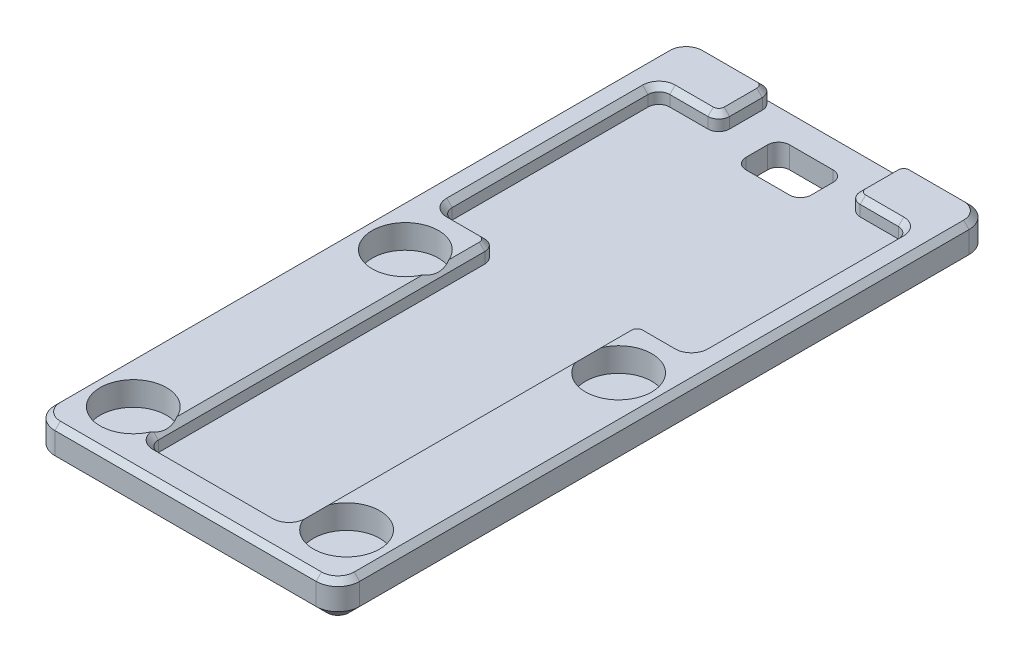
SolidWorks part; units mm, degrees
ref_plane "Front Plane" through (0, 0, 0) normal (0, 0, 1) x (1, 0, 0)
ref_plane "Top Plane" through (0, 0, 0) normal (0, 1, 0) x (1, 0, 0)
ref_plane "Right Plane" through (0, 0, 0) normal (1, 0, 0) x (0, 0, -1)
sketch "Sketch1" plane through (0, 0, 0) normal (0, 1, 0) x (1, 0, 0)
  line L1 (0, 0) -> (28, 0)
  line L2 (0, 0) -> (0, -60)
  line L3 (0, -60) -> (28, -60)
  line L4 (28, 0) -> (28, -60)
  line L5 (8, 0) -> (20, 0)
  line L6 (8, 0) -> (8, -5)
  line L7 (8, -5) -> (20, -5)
  line L8 (20, 0) -> (20, -5)
  line L9 (2.5, -5) -> (25.5, -5)
  line L10 (2.5, -5) -> (2.5, -25)
  line L11 (2.5, -25) -> (25.5, -25)
  line L12 (25.5, -5) -> (25.5, -25)
  line L13 (7.5, -25) -> (20.5, -25)
  line L14 (7.5, -25) -> (7.5, -57)
  line L15 (7.5, -57) -> (20.5, -57)
  line L16 (20.5, -25) -> (20.5, -57)
  circle A0 centre (23.8, -55) radius 3.05
  circle A1 centre (4.2, -30) radius 3.05
  circle A2 centre (23.8, -30) radius 3.05
  circle A3 centre (4.2, -55) radius 3.05
  point P13 (14, -5)
  point P14 (14, 0)
  point P19 (14, -25)
  point P20 (14, -25)
  dimension "D14" = 4.2
  dimension "D1" = 28
  dimension "D2" = 60
  dimension "D3" = 12
  dimension "D4" = 8
  dimension "D5" = 5
  dimension "D6" = 23
  dimension "D7" = 20
  dimension "D8" = 0
  dimension "D9" = 0
  dimension "D10" = 32
  dimension "D11" = 0
  dimension "D12" = 0
  dimension "D13" = 13
  dimension "D15" = 4.2
  dimension "D16" = 4.2
  dimension "D17" = 4.2
  dimension "D18" = 5
  dimension "D19" = 5
  dimension "D20" = 5
  dimension "D21" = 5
extrude "Boss-Extrude1" add sketch "Sketch1" along normal blind 3.5 contours L11 L16 L15 L14 L10 L9 L6 L1 L2 L3 L4 L8 L12 A3 A2 A1 A0 region at (4, 0, 0.6621)
extrude "Boss-Extrude2" add sketch "Sketch1<3>" along normal blind 2 contours L16 L11 L14 L15 | L12 L9 L7 L10 L11 | L8 L1 L6 L7 region at (14, 0, 2.5) region at (14, 0, 15) region at (14, 0, 41)
sketch "Sketch1<3>" plane through (0, 0, 0) normal (0, 1, 0) x (1, 0, 0) same geometry as "Sketch1"
extrude "Boss-Extrude3" add sketch "Sketch1<4>" along normal blind 1.3 contours A1 | A2 | A3 | A0 region at (23.8, 0, 55) region at (4.2, 0, 30) region at (23.8, 0, 30) region at (4.2, 0, 55)
sketch "Sketch1<4>" plane through (0, 0, 0) normal (0, 1, 0) x (1, 0, 0) same geometry as "Sketch1"
sketch "Sketch2" plane through (0, 2, 0) normal (0, 1, 0) x (1, 0, 0)
  line L0 (8, 0) -> (20, 0) construction
  line L1 (11, -2.5) -> (17, -2.5)
  line L2 (11, -2.5) -> (11, -6.5)
  line L3 (11, -6.5) -> (17, -6.5)
  line L4 (17, -2.5) -> (17, -6.5)
  point P6 (14, -6.5)
  point P7 (14, 0)
  dimension "D1" = 2.5
  dimension "D2" = 6
  dimension "D3" = 0
  dimension "D4" = 4
extrude "Cut-Extrude1" cut sketch "Sketch2" against normal blind 4
fillet "Fillet1" radius 1 4 edges at (11, 1, 6.5) (17, 1, 6.5) (17, 1, 2.5) (11, 1, 2.5)
fillet "Fillet2" radius 1 10 edges at (20.5, 2.75, 57) (7.5, 2.75, 57) (2.5, 2.75, 25) (7.5, 2.75, 25) (20.5, 2.75, 25) (25.5, 2.75, 25) (25.5, 2.75, 5) (20, 2.75, 5) (2.5, 2.75, 5) (8, 2.75, 5)
fillet "Fillet3" radius 1 2 edges at (20, 2.75, 0) (8, 2.75, 0)
fillet "Fillet4" radius 2 4 edges at (28, 1.75, 60) (0, 1.75, 60) (28, 1.75, 0) (0, 1.75, 0)
chamfer "Chamfer1" distance 1 angle 45 8 edges at (0, 0, 30) (0.5858, 0, 0.5858) (0.5858, 0, 59.4142) (14, 0, 0) (14, 0, 60) (27.4142, 0, 0.5858) (27.4142, 0, 59.4142) (28, 0, 30)
chamfer "Chamfer2" distance 0.5 angle 45 32 edges at (7.7929, 3.5, 56.7071) (7.5, 3.5, 41) (14, 3.5, 57) (7.2071, 3.5, 25.2929) (20.2071, 3.5, 56.7071) (5, 3.5, 25) (20.5, 3.5, 41) (2.7929, 3.5, 24.7071) (20.7929, 3.5, 25.2929) (2.5, 3.5, 15) (23, 3.5, 25) (2.7929, 3.5, 5.2929) (25.2071, 3.5, 24.7071) (5.25, 3.5, 5) (25.5, 3.5, 15) (7.7071, 3.5, 4.7071) (25.2071, 3.5, 5.2929) (8, 3.5, 2.5) (22.75, 3.5, 5) (7.7071, 3.5, 0.2929) (20.2929, 3.5, 4.7071) (4.5, 3.5, 0) (20, 3.5, 2.5) (0.5858, 3.5, 0.5858) (20.2929, 3.5, 0.2929) (0, 3.5, 30) (23.5, 3.5, 0) (0.5858, 3.5, 59.4142) (27.4142, 3.5, 0.5858) (14, 3.5, 60) (28, 3.5, 30) (27.4142, 3.5, 59.4142)
sketch "Sketch3" plane through (0, 0, 0) normal (0, -1, 0) x (1, 0, 0)
  line L0 (14.0455, 15.9773) -> (13.0946, 23.7497)
  line L1 (13.0946, 23.7497) -> (10.8054, 24.5292)
  line L2 (10.8054, 24.5292) -> (12.8866, 25.6341)
  line L3 (12.8866, 25.6341) -> (12.612, 28.1138)
  line L4 (12.612, 28.1138) -> (14.0201, 25.7119)
  line L5 (14.0201, 25.7119) -> (15.5028, 28.2043)
  line L6 (15.5028, 28.2043) -> (15.2028, 25.5944)
  line L7 (15.2028, 25.5944) -> (17.3205, 24.5276)
  line L8 (17.3205, 24.5276) -> (15.0218, 23.7656)
  line L9 (15.0218, 23.7656) -> (14.0455, 15.9773)
  line L10 (1, 58) -> (1, 2) construction
  spline S0 degree 3 poles (14.0979, 12.2435) (20.6397, 22.0968) (22.8461, 32.13) (23.6102, 42.4648) knots 0 0 0 0 1 1 1 1
  spline S1 degree 3 poles (23.6102, 42.4648) (19.3681, 37.0518) (15.6342, 33.5036) (12.8914, 31.8555) knots 0 0 0 0 1 1 1 1
  spline S2 degree 3 poles (12.8914, 31.8555) (9.8632, 30.0358) (7.2551, 32.914) (4.692, 40.02) knots 0 0 0 0 1 1 1 1
  spline S3 degree 3 poles (4.692, 40.02) (6.3927, 30.7469) (7.5686, 21.6724) (14.0979, 12.2435) knots 0 0 0 0 1 1 1 1
extrude "Cut-Extrude2" cut sketch "Sketch3" against normal blind 0.4
